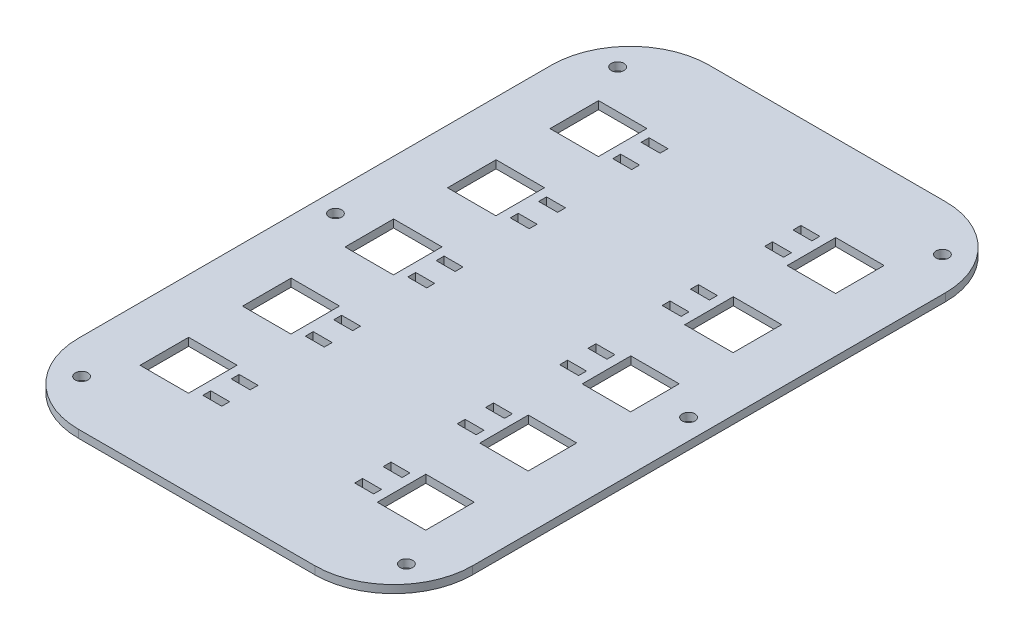
SolidWorks part; units mm, degrees
ref_plane "Front Plane" through (0, 0, 0) normal (0, 0, 1) x (1, 0, 0)
ref_plane "Top Plane" through (0, 0, 0) normal (0, 1, 0) x (1, 0, 0)
ref_plane "Right Plane" through (0, 0, 0) normal (1, 0, 0) x (0, 0, -1)
sketch "Sketch1" plane through (0, 0, 0) normal (0, 1, 0) x (1, 0, 0)
  line L1 (-75, 200) -> (75, 200)
  line L2 (-125, 150) -> (-125, -150)
  line L3 (-75, -200) -> (75, -200)
  line L4 (125, 150) -> (125, -150)
  arc A0 (-125, -150) -> (-75, -200) centre (-75, -150) ccw
  arc A1 (75, -200) -> (125, -150) centre (75, -150) ccw
  arc A2 (75, 200) -> (125, 150) centre (75, 150) cw
  arc A3 (-75, 200) -> (-125, 150) centre (-75, 150) ccw
  point P7 (-125, -200)
  point P10 (125, -200)
  point P13 (125, 200)
  dimension "D5" = 50
  dimension "D1" = 400
  dimension "D2" = 200
  dimension "D3" = 250
  dimension "D4" = 125
extrude "Boss-Extrude1" add sketch "Sketch1" along normal blind 5
sketch "Sketch3" plane through (0, 0, 0) normal (0, -1, 0) x (1, 0, 0)
  line L0 (-60.075, 145.1286) -> (-90.375, 145.1286) construction
  line L1 (-60.075, 145.1286) -> (-90.375, 145.1286)
  line L2 (-90.375, 145.1286) -> (-90.375, 114.7286) construction
  line L3 (-90.375, 114.7286) -> (-60.075, 114.7286) construction
  line L4 (-60.075, 114.7286) -> (-60.075, 145.1286) construction
  line L5 (-90.375, 145.1286) -> (-90.375, 114.7286)
  line L6 (-90.375, 114.7286) -> (-60.075, 114.7286)
  line L7 (-60.075, 114.7286) -> (-60.075, 145.1286)
  line L8 (90.375, 114.7286) -> (60.075, 114.7286) construction
  line L9 (90.375, 145.1286) -> (90.375, 114.7286) construction
  line L10 (60.075, 145.1286) -> (90.375, 145.1286) construction
  line L11 (60.075, 114.7286) -> (60.075, 145.1286) construction
  line L12 (90.375, 114.7286) -> (60.075, 114.7286)
  line L13 (90.375, 145.1286) -> (90.375, 114.7286)
  line L14 (60.075, 145.1286) -> (90.375, 145.1286)
  line L15 (60.075, 114.7286) -> (60.075, 145.1286)
  line L16 (-90.575, 145.3286) -> (-90.575, 114.5286)
  line L17 (-90.575, 114.5286) -> (-59.875, 114.5286)
  line L18 (-59.875, 114.5286) -> (-59.875, 145.3286)
  line L19 (-59.875, 145.3286) -> (-90.575, 145.3286)
  line L20 (59.875, 114.5286) -> (59.875, 145.3286)
  line L21 (59.875, 145.3286) -> (90.575, 145.3286)
  line L22 (90.575, 145.3286) -> (90.575, 114.5286)
  line L23 (90.575, 114.5286) -> (59.875, 114.5286)
  dimension "D1" = 0.2
  dimension "D2" = 0.2
extrude "Cut-Extrude1" cut sketch "Sketch3" against normal blind 10 contours L6 L7 L1 L5 | L18 L19 L16 L17 L7 L6 L5 L1 | L15 L12 L13 L14 | L23 L22 L21 L20 L12 L15 L14 L13 region at (-75.225, 0, 129.9286) region at (75.225, 0, 129.9286) region at (-75.225, 0, 145.2851) region at (59.9185, 0, 129.9286)
pattern_linear "LPattern1" count 5 spacing 65 along (0, 0, -1) of "Cut-Extrude1"
sketch "Sketch4" plane through (0, 5, 0) normal (0, 1, 0) x (1, 0, 0)
  line L0 (-36.75, -136.42) -> (-59.75, -136.42) construction
  line L1 (-36.75, -136.42) -> (-59.75, -136.42)
  line L2 (-33.75, -124.42) -> (-59.75, -124.42) construction
  line L3 (-33.75, -124.42) -> (-59.75, -124.42)
  line L4 (-42.165, -123.92) -> (-54.165, -123.92)
  line L5 (-42.165, -136.92) -> (-54.165, -136.92)
  line L6 (-54.165, -136.92) -> (-54.165, -141.92)
  line L7 (-54.165, -141.92) -> (-42.165, -141.92)
  line L8 (-42.165, -141.92) -> (-42.165, -136.92)
  line L9 (-36.75, -136.92) -> (-59.75, -136.92) construction
  line L11 (-33.75, -123.92) -> (-59.75, -123.92) construction
  line L12 (-54.165, -118.92) -> (-42.165, -118.92)
  line L17 (-54.165, -118.92) -> (-54.165, -123.92)
  line L18 (-54.165, -123.92) -> (-42.165, -123.92)
  line L19 (-42.165, -118.92) -> (-42.165, -123.92)
  line L20 (0, -200) -> (0, -445.0301) construction
  line L21 (-75, -200) -> (75, -200) construction
  line L22 (54.165, -141.92) -> (42.165, -141.92)
  line L23 (42.165, -141.92) -> (42.165, -136.92)
  line L24 (42.165, -136.92) -> (54.165, -136.92)
  line L25 (54.165, -136.92) -> (54.165, -141.92)
  line L26 (42.165, -123.92) -> (54.165, -123.92)
  line L27 (42.165, -118.92) -> (42.165, -123.92)
  line L28 (54.165, -118.92) -> (42.165, -118.92)
  line L29 (54.165, -118.92) -> (54.165, -123.92)
  line L30 (-54.165, -141.92) -> (-54.165, -136.92) construction
  dimension "D3" = 5
  dimension "D4" = 12
  dimension "D6" = 5
  dimension "D1" = 0.5
  dimension "D2" = 0.5
extrude "Cut-Extrude2" cut sketch "Sketch4" against normal blind 10 contours L7 L8 L5 L6 | L19 L12 L17 L4 | L25 L24 L23 L22 | L29 L28 L27 L26 region at (-48.165, 5, 121.42) region at (-48.165, 5, 139.42) region at (48.165, 5, 139.42) region at (48.165, 5, 121.42)
pattern_linear "LPattern2" count 5 spacing 65 along (0, 0, -1) of "Cut-Extrude2"
sketch "Sketch5" plane through (0, 5, 0) normal (0, 1, 0) x (1, 0, 0)
  circle A0 centre (-103, 170) radius 4
  circle A1 centre (103, 170) radius 4
  circle A2 centre (103, -170) radius 4
  circle A3 centre (-103, -170) radius 4
  circle A4 centre (-112, 0) radius 4
  circle A5 centre (112, 0) radius 4
  dimension "D1" = 8
  dimension "D2" = 22
  dimension "D3" = 30
  dimension "D4" = 22
  dimension "D5" = 30
  dimension "D6" = 112
  dimension "D7" = 112
extrude "Cut-Extrude3" cut sketch "Sketch5" against normal blind 5
